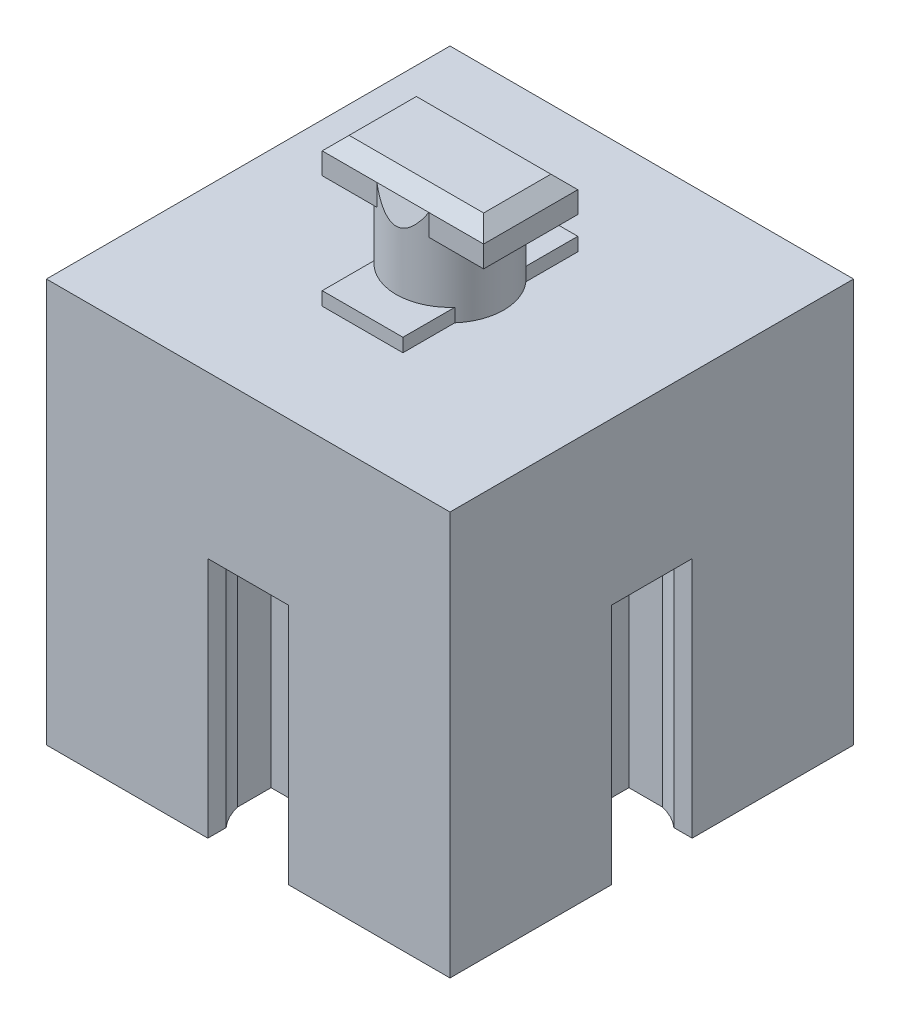
SolidWorks part; units mm, degrees
ref_plane "前视基准面" through (0, 0, 0) normal (0, 0, 1) x (1, 0, 0)
ref_plane "上视基准面" through (0, 0, 0) normal (0, 1, 0) x (1, 0, 0)
ref_plane "右视基准面" through (0, 0, 0) normal (1, 0, 0) x (0, 0, -1)
sketch "草图1" plane through (0, 0, 0) normal (0, 1, 0) x (1, 0, 0)
  line L0 (7.5, 7.5) -> (7.5, -7.5)
  line L1 (7.5, 7.5) -> (-7.5, 7.5)
  line L2 (7.5, -7.5) -> (-7.5, -7.5)
  line L3 (-7.5, 7.5) -> (-7.5, -7.5)
  line L4 (7.5, 7.5) -> (-7.5, -7.5) construction
  line L5 (7.5, -7.5) -> (-7.5, 7.5) construction
  point P1 (0, 0)
  dimension "D1" = 15
  dimension "D2" = 15
extrude "凸台-拉伸1" add sketch "草图1" along normal blind 15
sketch "草图2" plane through (0, 0, 0) normal (0, -1, 0) x (1, 0, 0)
  line L0 (0, 7.5) -> (0, 5.5) construction
  line L2 (-7.5, 7.5) -> (7.5, 7.5) construction
  line L3 (0, 5.5) -> (0, 4.7) construction
  line L4 (1.5, 7.5) -> (-1.5, 7.5)
  line L5 (-1.5, 7.5) -> (-1.5, 6.8229)
  line L6 (1.95, 4.7) -> (-1.95, 4.7)
  line L7 (-1.95, 4.7) -> (-1.95, 5.9444)
  line L8 (1.95, 4.7) -> (1.95, 5.9444)
  line L9 (1.5, 7.5) -> (1.5, 6.8229)
  arc A0 (-1.5, 6.8229) -> (-1.95, 5.9444) centre (0, 5.5) ccw
  arc A1 (1.5, 6.8229) -> (1.95, 5.9444) centre (0, 5.5) cw
  dimension "D5" = 2
  dimension "D1" = 2
  dimension "D2" = 0.8
  dimension "D3" = 1.5
  dimension "D4" = 1.95
extrude "切除-拉伸1" cut sketch "草图2" against normal blind 9
sketch "草图4" plane through (0, 15, 0) normal (0, 1, 0) x (1, 0, 0)
  line L0 (1.5, -3.25) -> (-1.5, -3.25)
  line L1 (1.5, -3.25) -> (1.5, 3.25)
  line L2 (-1.5, -3.25) -> (-1.5, 3.25)
  line L3 (1.5, 3.25) -> (-1.5, 3.25)
  line L4 (1.5, -3.25) -> (-1.5, 3.25) construction
  line L5 (-1.5, -3.25) -> (1.5, 3.25) construction
  point P1 (0, 0)
  dimension "D1" = 3
  dimension "D2" = 6.5
extrude "凸台-拉伸2" add sketch "草图4" along normal blind 0.5
sketch "草图6" plane through (0, 15.5, 0) normal (0, 1, 0) x (1, 0, 0)
  circle A0 centre (0, 0) radius 2
  dimension "D1" = 4
extrude "凸台-拉伸3" add sketch "草图6" along normal blind 2.2 and the other way blind 0.5
sketch "草图7" plane through (0, 17.7, 0) normal (0, 1, 0) x (1, 0, 0)
  line L0 (3, 1.75) -> (3, -1.75)
  line L1 (3, 1.75) -> (-3, 1.75)
  line L2 (3, -1.75) -> (-3, -1.75)
  line L3 (-3, 1.75) -> (-3, -1.75)
  line L4 (3, 1.75) -> (-3, -1.75) construction
  line L5 (3, -1.75) -> (-3, 1.75) construction
  point P1 (0, 0)
  dimension "D1" = 3.5
  dimension "D2" = 6
extrude "凸台-拉伸4" add sketch "草图7" along normal blind 1.3
sketch "草图8" plane through (0, 17.7, 0) normal (0, 1, 0) x (1, 0, 0)
  circle A0 centre (0, 0) radius 2
extrude "凸台-拉伸5" add sketch "草图8" along normal blind 0.8
chamfer "倒角1" distance 0.5 angle 45 4 edges at (-3, 19, 0) (0, 19, -1.75) (3, 19, 0) (0, 19, 1.75)
sketch "草图9" plane through (0, 0, 0) normal (1, 0, 0) x (0, 0, -1)
  line L0 (-1.75, 17.7) -> (-2, 17.7)
  line L1 (-2, 17.7) -> (-2, 18.5)
  line L2 (-2, 18.5) -> (-1.75, 18.5)
  line L3 (-1.75, 18.5) -> (-2, 17.7)
  line L4 (0, 18.5) -> (0, 17.3973) construction
  line L5 (1.75, 18.5) -> (-1.75, 18.5) construction
  line L6 (1.75, 18.5) -> (2, 17.7)
  line L7 (2, 17.7) -> (2, 18.5)
  line L8 (2, 18.5) -> (1.75, 18.5)
  dimension "D1" = 0.25
  dimension "D2" = 0.8
  dimension "D3" = 0.25
extrude "切除-拉伸2" cut sketch "草图9" against normal blind 2 and the other way blind 2 contours L1 L2 L3 | L7 L8 L6
pattern_circular "阵列(圆周)1" count 4 over 360 about axis through (0, 15, 0) along (0, 1, 0) of "切除-拉伸1"
sketch "草图10" plane through (0, 0, 0) normal (0, -1, 0) x (1, 0, 0)
  line L0 (6.8, 6.8) -> (6.8, 5.3)
  line L1 (6.8, 6.8) -> (5.3, 6.8)
  line L2 (5.3, 6.8) -> (2.5, 4)
  line L3 (4, 2.5) -> (4, -2.5)
  line L4 (4, 4) -> (-4, -4) construction
  line L5 (4, -4) -> (-4, 4) construction
  line L6 (2.5, 4) -> (-2.5, 4)
  line L7 (-6.8, 5.3) -> (-4, 2.5)
  line L8 (-6.8, 6.8) -> (-6.8, 5.3)
  line L9 (2.5, -4) -> (-2.5, -4)
  line L10 (6.8, 6.8) -> (-6.8, -6.8) construction
  line L11 (6.8, -6.8) -> (-6.8, 6.8) construction
  line L12 (-6.8, 6.8) -> (-5.3, 6.8)
  line L13 (-5.3, 6.8) -> (-2.5, 4)
  line L14 (-4, 2.5) -> (-4, -2.5)
  line L15 (6.8, 5.3) -> (4, 2.5)
  line L16 (6.8, -6.8) -> (5.3, -6.8)
  line L17 (6.8, -6.8) -> (6.8, -5.3)
  line L18 (6.8, -5.3) -> (4, -2.5)
  line L19 (4, 4) -> (-4, -4) construction
  line L20 (4, -4) -> (-4, 4) construction
  line L21 (5.3, -6.8) -> (2.5, -4)
  line L22 (-6.8, -6.8) -> (-6.8, -5.3)
  line L23 (-6.8, -6.8) -> (-5.3, -6.8)
  line L24 (-5.3, -6.8) -> (-2.5, -4)
  line L27 (-6.8, -5.3) -> (-4, -2.5)
  circle A0 centre (0, 0) radius 4 construction
  point P1 (0, 0)
  point P37 (0, 0)
  dimension "D1" = 8
  dimension "D2" = 8
  dimension "D3" = 13.6
  dimension "D4" = 13.6
  dimension "D5" = 1.5
  dimension "D6" = 8
  dimension "D8" = 8
  dimension "D7" = 4
extrude "切除-拉伸3" cut sketch "草图10" against normal blind 13.6
